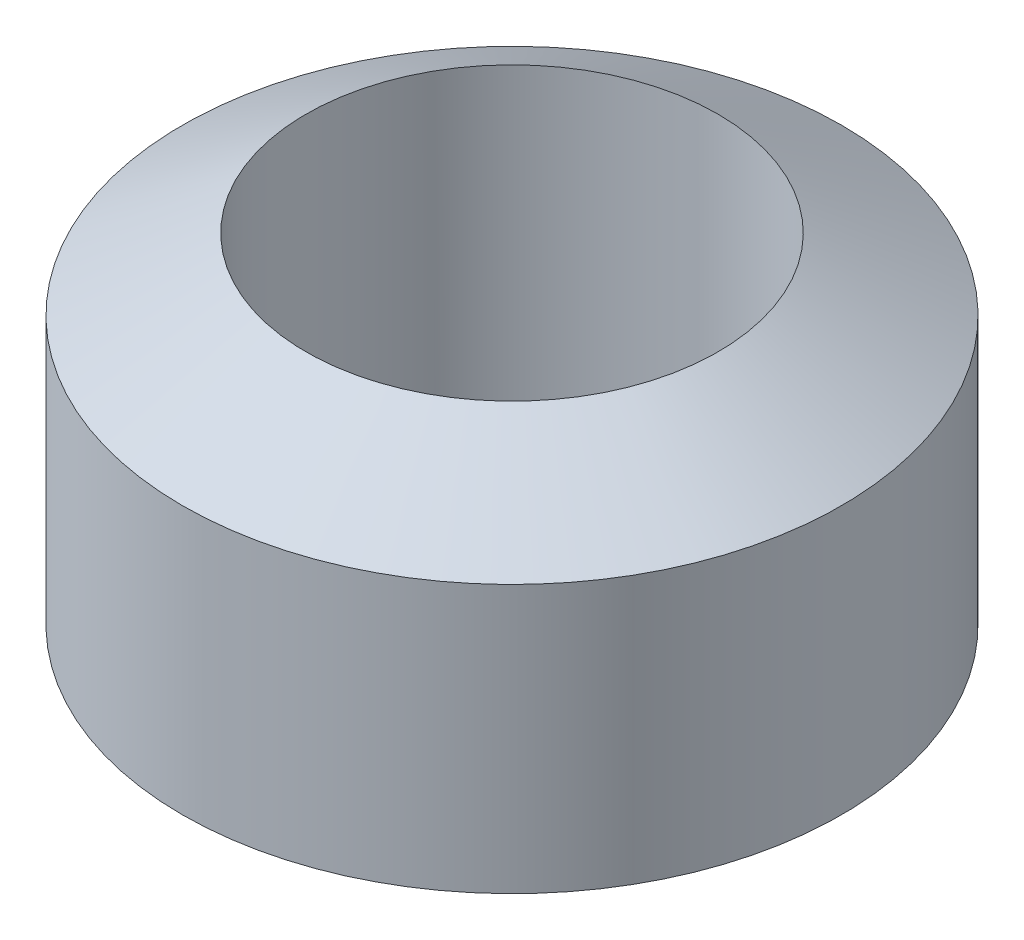
SolidWorks part; units mm, degrees
material "Rubber"
ref_plane "Спереди" through (0, 0, 0) normal (0, 0, 1) x (1, 0, 0)
ref_plane "Сверху" through (0, 0, 0) normal (0, 1, 0) x (1, 0, 0)
ref_plane "Справа" through (0, 0, 0) normal (1, 0, 0) x (0, 0, -1)
other "Configuration Table"
sketch "Sketch2" plane through (0, 0, 0) normal (0, 1, 0) x (1, 0, 0)
  circle A0 centre (0, 0) radius 8
  circle A1 centre (0, 0) radius 5
  dimension "D1" = 16
  dimension "D2" = 10
extrude "Boss-Extrude1" add sketch "Sketch2" along normal blind 10
chamfer "Chamfer3" distance 1.75 angle 60 1 edges at (0, 10, 8) first distance on face at (0, 10, 8)
chamfer "Chamfer4" distance 1.75 angle 60 1 edges at (0, 0, 8) first distance on face at (0, 8.25, 8)
